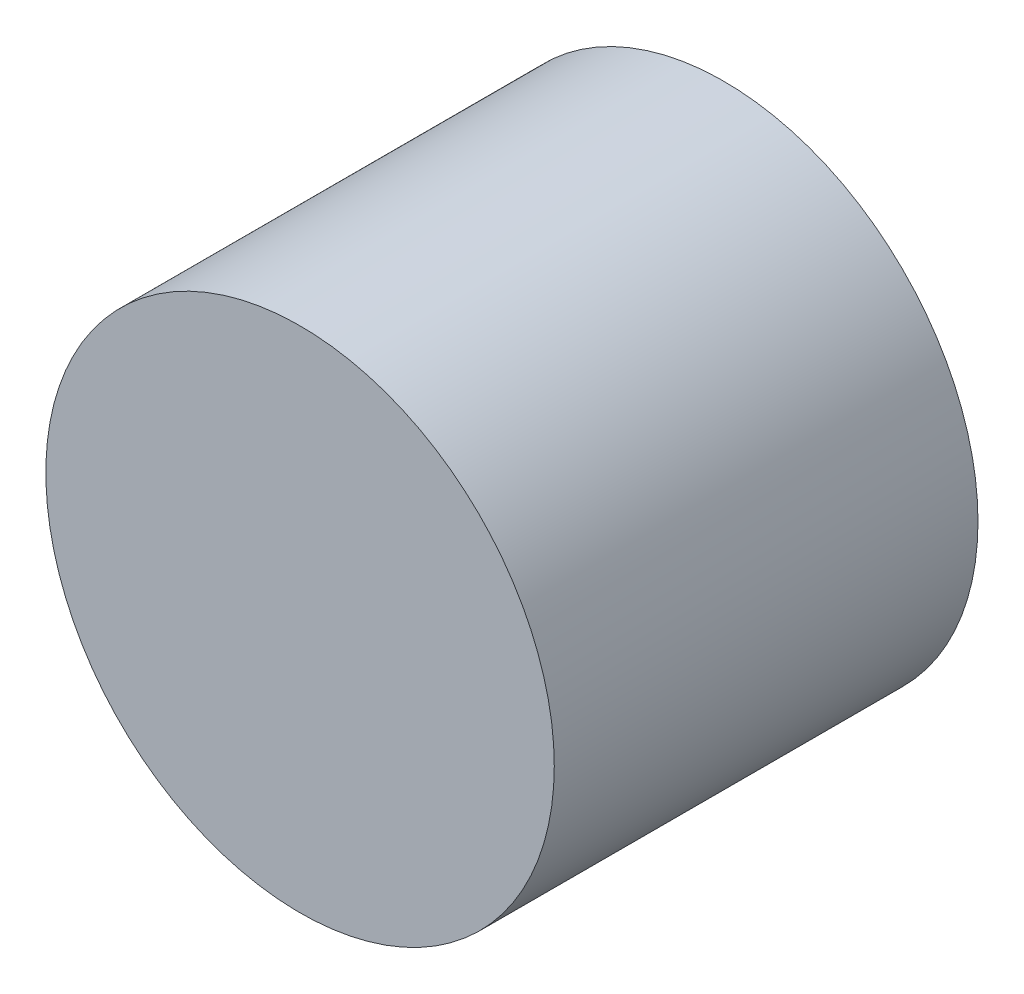
SolidWorks part; units mm, degrees
ref_plane "Front Plane" through (0, 0, 0) normal (0, 0, 1) x (1, 0, 0)
ref_plane "Top Plane" through (0, 0, 0) normal (0, 1, 0) x (1, 0, 0)
ref_plane "Right Plane" through (0, 0, 0) normal (1, 0, 0) x (0, 0, -1)
sketch "Sketch1" plane through (0, 0, 0) normal (0, 0, 1) x (1, 0, 0)
  circle A0 centre (-68.3905, -10.4636) radius 6
  point P2 (-76.6557, -11.6334)
  point P3 (-68.3905, -10.4636)
  dimension "D1" = 12
extrude "Boss-Extrude3" add sketch "Sketch1" along normal blind 10
sketch "Sketch3" plane through (0, 0, 0) normal (0, 0, -1) x (-1, 0, 0)
  line L0 (70.9885, -11.9636) -> (65.7924, -11.9636)
  arc A0 (70.9885, -11.9636) -> (65.7924, -11.9636) centre (68.3905, -10.4636) ccw
  dimension "D1" = 6
  dimension "D2" = 4.5
extrude "Cut-Extrude1" cut sketch "Sketch3" against normal blind 8
sketch "Sketch4" plane through (0, 0, 0) normal (0, 0, -1) x (-1, 0, 0)
  circle A0 centre (68.3905, -10.4636) radius 4.5
  dimension "D1" = 9
extrude "Cut-Extrude2" cut sketch "Sketch4" against normal blind 3
